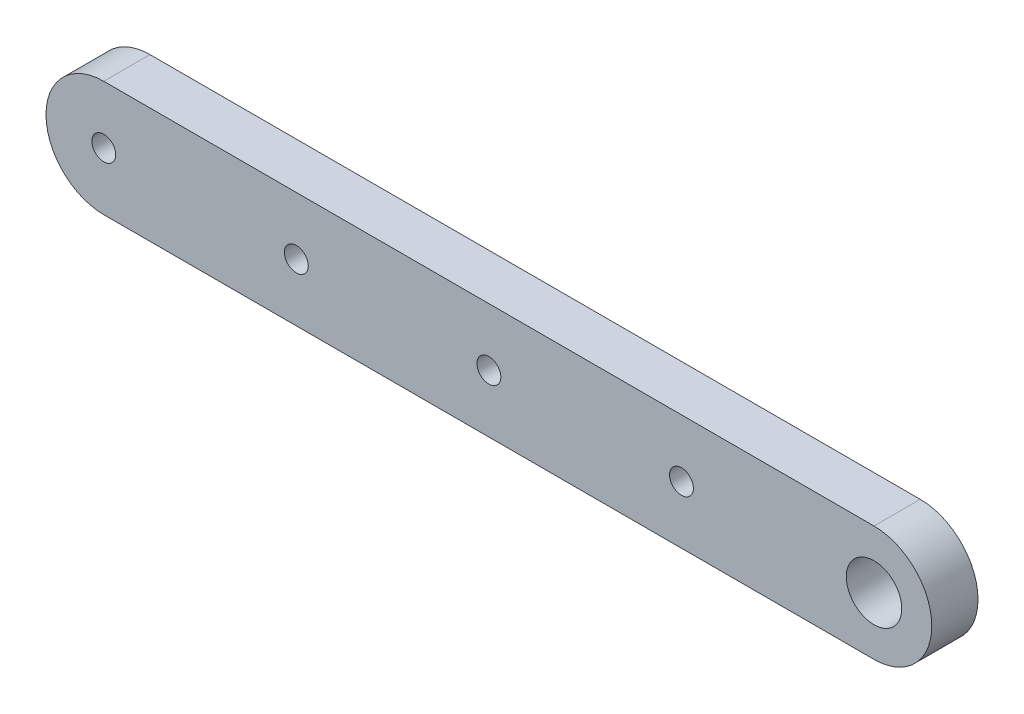
SolidWorks part; units mm, degrees
material "Pine"
ref_plane "Front Plane" through (0, 0, 0) normal (0, 0, 1) x (1, 0, 0)
ref_plane "Top Plane" through (0, 0, 0) normal (0, 1, 0) x (1, 0, 0)
ref_plane "Right Plane" through (0, 0, 0) normal (1, 0, 0) x (0, 0, -1)
sketch "Sketch1" plane through (0, 0, 0) normal (0, 0, 1) x (1, 0, 0)
  line L0 (0, 7.5) -> (100, 7.5)
  line L1 (100, -7.5) -> (0, -7.5)
  circle A0 centre (0, 0) radius 7.5
  circle A1 centre (100, 0) radius 7.5
  dimension "D1" = 100
  dimension "D2" = 15
extrude "Boss-Extrude1" add sketch "Sketch1" along normal blind 6 contours A1 L0 A0 L1 | A1 | A0 region at (50, 0, 0) region at (0, 0, 0) region at (100, 0, 0)
ref_plane "Plane1" through (0, 0, 3) normal (0, 0, 1) x (1, 0, 0)
sketch "Sketch2" plane through (0, 0, 6) normal (0, 0, 1) x (1, 0, 0)
  circle A0 centre (0, 0) radius 1.55
  circle A1 centre (100, 0) radius 1.55
  dimension "D1" = 3.1
extrude "Cut-Extrude1" cut sketch "Sketch2" against normal through all
pattern_linear "LPattern1" count 4 spacing 25 along (1, 0, 0) of "Cut-Extrude1"
sketch "Sketch3" plane through (0, 0, 6) normal (0, 0, 1) x (1, 0, 0)
  circle A0 centre (100, 0) radius 3.6
  dimension "D1" = 7.2
extrude "Cut-Extrude2" cut sketch "Sketch3" against normal through all
